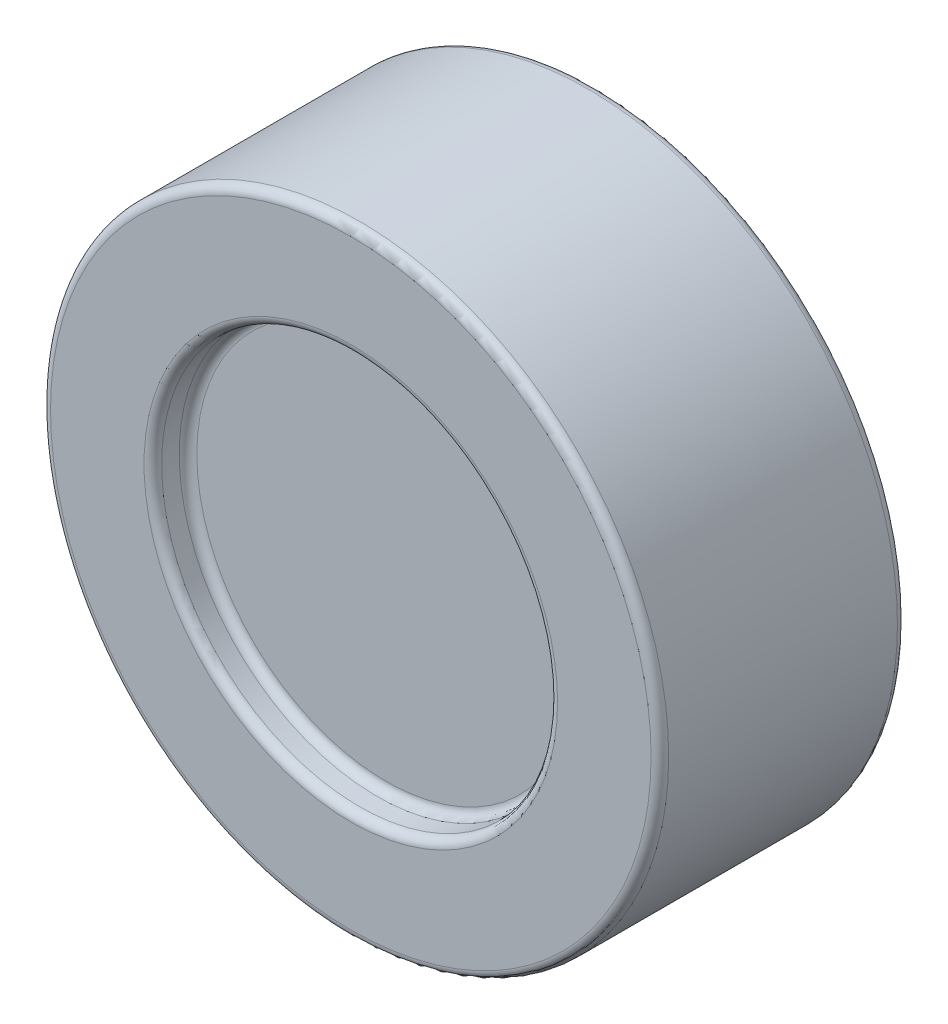
SolidWorks part; units mm, degrees
ref_plane "Plan de face" through (0, 0, 0) normal (0, 0, 1) x (1, 0, 0)
ref_plane "Plan de dessus" through (0, 0, 0) normal (0, 1, 0) x (1, 0, 0)
ref_plane "Plan de droite" through (0, 0, 0) normal (1, 0, 0) x (0, 0, -1)
sketch "Esquisse1" plane through (0, 0, 0) normal (0, 0, 1) x (1, 0, 0)
  circle A0 centre (0, 0) radius 35.125
  circle A1 centre (0, 0) radius 22.5
  dimension "D1" = 45
  dimension "D2" = 70.25
extrude "Boss.-Extru.1" add sketch "Esquisse1" along normal blind 24 contours A1 region at (0, 0, 0)
extrude "Boss.-Extru.2" add sketch "Esquisse1<4>" along normal blind 28
sketch "Esquisse1<4>" plane through (0, 0, 0) normal (0, 0, 1) x (1, 0, 0) same geometry as "Esquisse1"
fillet "Congé1" radius 1 4 edges at (22.5, 0, 28) (22.5, 0, 24) (35.125, 0, 0) (35.125, 0, 28)
